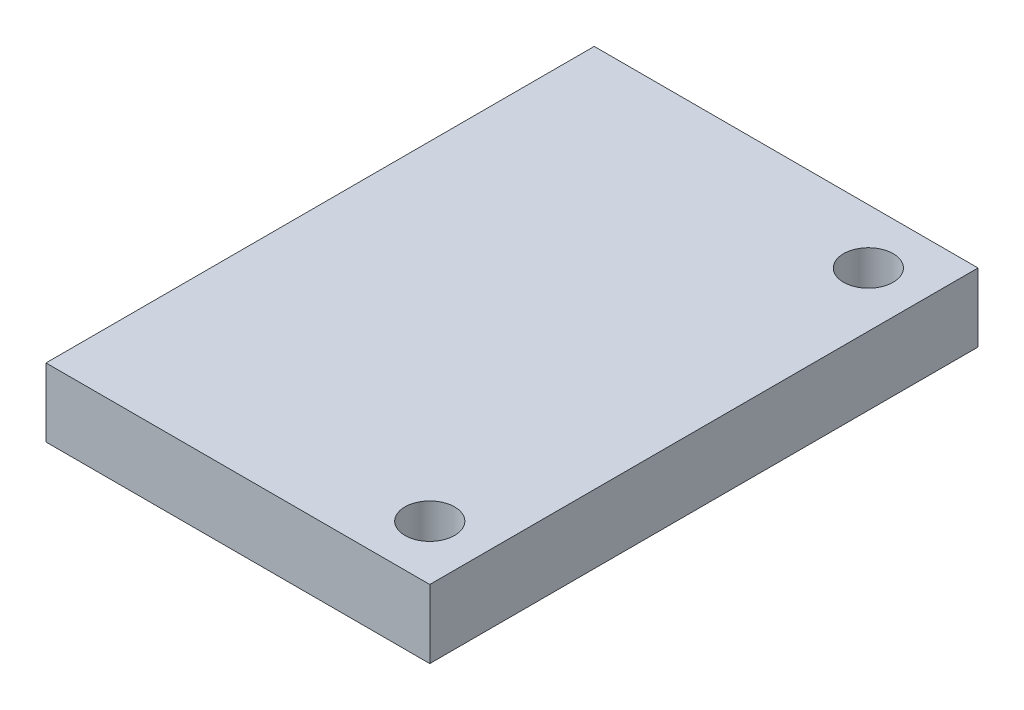
SolidWorks part; units mm, degrees
ref_plane "Front Plane" through (0, 0, 0) normal (0, 0, 1) x (1, 0, 0)
ref_plane "Top Plane" through (0, 0, 0) normal (0, 1, 0) x (1, 0, 0)
ref_plane "Right Plane" through (0, 0, 0) normal (1, 0, 0) x (0, 0, -1)
sketch "Sketch2" plane through (0, 0, 0) normal (0, 1, 0) x (1, 0, 0)
  line L1 (-8.89, 12.7) -> (8.89, 12.7)
  line L2 (-8.89, 12.7) -> (-8.89, -12.7)
  line L3 (-8.89, -12.7) -> (8.89, -12.7)
  line L4 (8.89, 12.7) -> (8.89, -12.7)
  line L5 (-8.89, 12.7) -> (8.89, -12.7) construction
  line L6 (-8.89, -12.7) -> (8.89, 12.7) construction
  point P0 (0, 0)
  dimension "D1" = 17.78
  dimension "D2" = 25.4
extrude "Boss-Extrude1" add sketch "Sketch2" along normal blind 3.175
sketch "Sketch3" plane through (0, 3.175, 0) normal (0, 1, 0) x (1, 0, 0)
  line L0 (-8.89, 12.7) -> (-8.89, -12.7) construction
  line L1 (-8.89, 10.16) -> (6.35, 10.16) construction
  line L2 (-8.89, 10.16) -> (-8.89, -10.16) construction
  line L3 (-8.89, -10.16) -> (6.35, -10.16) construction
  line L4 (6.35, 10.16) -> (6.35, -10.16) construction
  line L6 (-8.89, 0) -> (8.89, 0) construction
  line L7 (8.89, -12.7) -> (8.89, 12.7) construction
  circle A0 centre (6.35, 10.16) radius 1.15
  circle A1 centre (6.35, -10.16) radius 1.15
  dimension "D1" = 2.3
  dimension "D2" = 15.24
  dimension "D3" = 20.32
extrude "Cut-Extrude1" cut sketch "Sketch3" against normal up to surface (3.175 mm away) up to face at (0, 0, 0)
